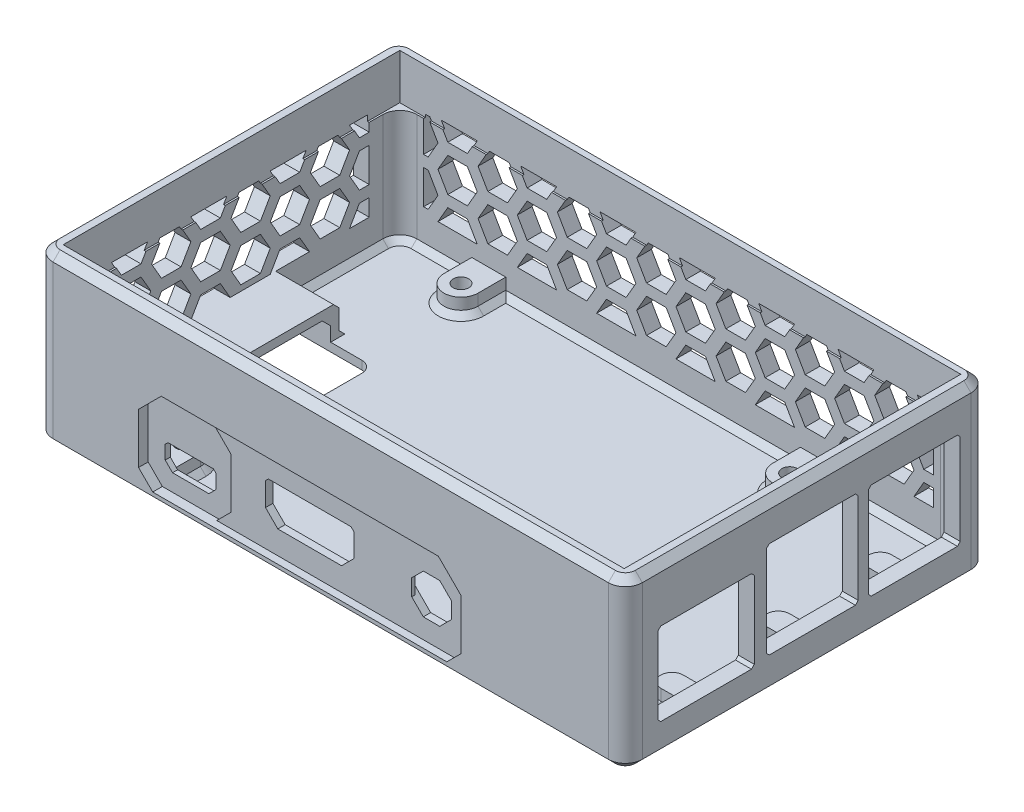
SolidWorks part; units mm, degrees
ref_plane "Front Plane" through (0, 0, 0) normal (0, 0, 1) x (1, 0, 0)
ref_plane "Top Plane" through (0, 0, 0) normal (0, 1, 0) x (1, 0, 0)
ref_plane "Right Plane" through (0, 0, 0) normal (1, 0, 0) x (0, 0, -1)
sketch "Sketch1" plane through (0, 0, 0) normal (0, 1, 0) x (1, 0, 0)
  line L0 (1, 28) -> (0, 28) construction
  line L1 (0, 0) -> (-85, 0) construction
  line L2 (0, 0) -> (0, 56) construction
  line L3 (0, 56) -> (-85, 56) construction
  line L4 (-85, 0) -> (-85, 56) construction
  line L5 (-97, 57.2) -> (1, 57.2) construction
  line L6 (-97, 57.2) -> (-97, -1.2) construction
  line L7 (-97, -1.2) -> (1, -1.2) construction
  line L8 (1, 57.2) -> (1, -1.2) construction
  circle A0 centre (-81.5, 52.5) radius 1.375 construction
  circle A1 centre (-23.5, 52.5) radius 1.375 construction
  circle A2 centre (-81.5, 3.5) radius 1.375 construction
  circle A3 centre (-23.5, 3.5) radius 1.375 construction
  dimension "D3" = 2.75
  dimension "D1" = 56
  dimension "D2" = 85
  dimension "D4" = 49
  dimension "D5" = 58
  dimension "D6" = 3.5
  dimension "D7" = 3.5
  dimension "D8" = 98
  dimension "D9" = 58.4
  dimension "D10" = 15.5
sketch "Sketch2" plane through (0, 0, 0) normal (0, 1, 0) x (1, 0, 0)
  line L0 (-84.5, -2.5) -> (-84.5, 3.5)
  line L2 (-78.5, 3.5) -> (-78.5, -2.5)
  line L3 (-81.5, 3.5) -> (-23.5, 3.5) construction
  line L4 (-81.5, 3.5) -> (-81.5, 52.5) construction
  line L5 (-52.5, 3.5) -> (-52.5, 28) construction
  line L6 (-52.5, 28) -> (-81.5, 28) construction
  line L7 (-84.5, -2.5) -> (-78.5, -2.5)
  line L8 (-20.5, -2.5) -> (-26.5, -2.5)
  line L9 (-26.5, 3.5) -> (-26.5, -2.5)
  line L10 (-20.5, -2.5) -> (-20.5, 3.5)
  line L11 (-20.5, 58.5) -> (-20.5, 52.5)
  line L12 (-26.5, 52.5) -> (-26.5, 58.5)
  line L13 (-20.5, 58.5) -> (-26.5, 58.5)
  line L14 (-84.5, 58.5) -> (-78.5, 58.5)
  line L15 (-78.5, 52.5) -> (-78.5, 58.5)
  line L16 (-84.5, 58.5) -> (-84.5, 52.5)
  arc A0 (-84.5, 3.5) -> (-78.5, 3.5) centre (-81.5, 3.5) cw
  circle A1 centre (-81.5, 3.5) radius 1.375 construction
  circle A2 centre (-81.5, 3.5) radius 1.375
  circle A3 centre (-23.5, 3.5) radius 1.375
  arc A4 (-20.5, 3.5) -> (-26.5, 3.5) centre (-23.5, 3.5) ccw
  arc A5 (-20.5, 52.5) -> (-26.5, 52.5) centre (-23.5, 52.5) cw
  circle A6 centre (-23.5, 52.5) radius 1.375
  circle A7 centre (-81.5, 52.5) radius 1.375
  arc A8 (-84.5, 52.5) -> (-78.5, 52.5) centre (-81.5, 52.5) ccw
  dimension "D1" = 2.75
  dimension "D2" = 6
  dimension "D3" = 6
extrude "Boss-Extrude1" add sketch "Sketch2" along normal blind 4.5
sketch "Sketch4" plane through (0, 0, 0) normal (0, 1, 0) x (1, 0, 0)
  line L0 (0, 28) -> (4, 28) construction
  line L1 (-100, 60) -> (4, 60)
  line L2 (-100, 60) -> (-100, -4)
  line L3 (-100, -4) -> (4, -4)
  line L4 (4, 60) -> (4, -4)
  line L5 (0, 0) -> (0, 56) construction
  line L7 (1, 57.2) -> (1, -1.2) construction
  line L9 (-97, 57.2) -> (-97, -1.2) construction
  dimension "D1" = 64
  dimension "D2" = 3
  dimension "D3" = 3
extrude "Boss-Extrude2" add sketch "Sketch4" along normal blind 1.5
sketch "Sketch5" plane through (0, 0, 0) normal (0, -1, 0) x (1, 0, 0)
  circle A0 centre (-81.5, -3.5) radius 2.6
  circle A1 centre (-23.5, -3.5) radius 2.6
  circle A2 centre (-23.5, -52.5) radius 2.6
  circle A3 centre (-81.5, -52.5) radius 2.6
  dimension "D1" = 5.2
extrude "Cut-Extrude1" cut sketch "Sketch5" against normal offset from surface (2.5 mm away) 2 up to face at (-81.5, 4.5, -1.25)
sketch "Sketch6" plane through (0, 1.5, 0) normal (0, 1, 0) x (1, 0, 0)
  line L0 (-97, 57.2) -> (-97, -1.2) construction
  line L1 (-100, 60) -> (4, 60)
  line L2 (-100, 60) -> (-100, -4)
  line L3 (-100, -4) -> (4, -4)
  line L4 (4, 60) -> (4, -4)
  line L5 (-97.5, 57.7) -> (1.5, 57.7)
  line L6 (-97.5, 57.7) -> (-97.5, -1.7)
  line L7 (-97.5, -1.7) -> (1.5, -1.7)
  line L8 (1.5, 57.7) -> (1.5, -1.7)
  line L9 (-97, 57.2) -> (1, 57.2) construction
  line L10 (1, 57.2) -> (1, -1.2) construction
  line L11 (-97, -1.2) -> (1, -1.2) construction
  dimension "D1" = 0.5
  dimension "D2" = 0.5
  dimension "D3" = 0.5
  dimension "D4" = 0.5
extrude "Boss-Extrude3" add sketch "Sketch6" along normal blind 28
sketch "Sketch10" plane through (0, 1.5, 0) normal (0, 1, 0) x (1, 0, 0)
  line L0 (1.5, 49) -> (-2, 49)
  line L1 (1.5, -1.7) -> (1.5, 57.7) construction
  line L2 (-2, 45) -> (1.5, 45)
  line L3 (1.5, 45) -> (1.5, 49)
  line L4 (1.5, 31) -> (-2, 31)
  line L5 (-2, 27) -> (1.5, 27)
  line L6 (1.5, 27) -> (1.5, 31)
  line L7 (1.5, 12.25) -> (-2, 12.25)
  line L8 (-2, 8.25) -> (1.5, 8.25)
  line L9 (1.5, 8.25) -> (1.5, 12.25)
  line L10 (0, 0) -> (0, 56) construction
  arc A0 (-2, 49) -> (-2, 45) centre (-2, 47) ccw
  arc A1 (-2, 31) -> (-2, 27) centre (-2, 29) ccw
  arc A2 (-2, 12.25) -> (-2, 8.25) centre (-2, 10.25) ccw
  point P19 (-4, 47)
  dimension "D1" = 4
  dimension "D2" = 4
  dimension "D3" = 10.25
  dimension "D4" = 29
  dimension "D5" = 47
extrude "Boss-Extrude4" add sketch "Sketch10" along normal up to surface (3 mm away) up to face at (-23.5, 4.5, -54.35)
sketch "Sketch18" plane through (0, 1.5, 0) normal (0, 1, 0) x (1, 0, 0)
  line L0 (-97.2, 57.4) -> (1.2, 57.4)
  line L1 (-97.5, 57.7) -> (1.5, 57.7)
  line L2 (-97.5, 57.7) -> (-97.5, -1.7)
  line L3 (-97.5, -1.7) -> (1.5, -1.7)
  line L4 (1.5, 57.7) -> (1.5, -1.7)
  line L5 (1.2, 57.4) -> (1.2, -1.4)
  line L6 (-97.2, -1.4) -> (1.2, -1.4)
  line L7 (-97.2, 57.4) -> (-97.2, -1.4)
  dimension "D1" = 0.3
extrude "Boss-Extrude6" add sketch "Sketch18" along normal blind 20
sketch "Sketch19" plane through (0, 0, -60) normal (0, 0, -1) x (-1, 0, 0)
  line L4 (5.5981, 8.5) -> (7.3301, 9.5) construction
  line L5 (6.4641, 7) -> (4.7321, 10)
  line L6 (4.7321, 10) -> (1.2679, 10)
  line L7 (1.2679, 10) -> (-0.4641, 7)
  line L8 (3, 7) -> (93, 7)
  line L9 (93, 7) -> (93, 22.5)
  line L10 (93, 22.5) -> (3, 22.5)
  line L11 (3, 22.5) -> (3, 7)
  line L12 (3, 7) -> (93, 7)
  line L13 (93, 7) -> (93, 22.5)
  line L14 (93, 22.5) -> (3, 22.5)
  line L15 (3, 22.5) -> (3, 7)
  line L16 (-0.4641, 7) -> (1.2679, 4)
  line L17 (1.2679, 4) -> (4.7321, 4)
  line L18 (4.7321, 4) -> (6.4641, 7)
  line L19 (11.6603, 14) -> (8.1962, 14)
  line L20 (8.1962, 14) -> (6.4641, 11)
  line L21 (6.4641, 11) -> (8.1962, 8)
  line L22 (8.1962, 8) -> (11.6603, 8)
  line L23 (11.6603, 8) -> (13.3923, 11)
  line L24 (13.3923, 11) -> (11.6603, 14)
  line L25 (20.4641, 7) -> (18.7321, 10)
  line L26 (18.7321, 10) -> (15.2679, 10)
  line L27 (15.2679, 10) -> (13.5359, 7)
  line L28 (13.5359, 7) -> (15.2679, 4)
  line L29 (15.2679, 4) -> (18.7321, 4)
  line L30 (18.7321, 4) -> (20.4641, 7)
  line L31 (25.6603, 14) -> (22.1962, 14)
  line L32 (22.1962, 14) -> (20.4641, 11)
  line L33 (20.4641, 11) -> (22.1962, 8)
  line L34 (22.1962, 8) -> (25.6603, 8)
  line L35 (25.6603, 8) -> (27.3923, 11)
  line L36 (27.3923, 11) -> (25.6603, 14)
  line L37 (19.5981, 8.5) -> (21.3301, 9.5) construction
  line L38 (34.4641, 7) -> (32.7321, 10)
  line L39 (32.7321, 10) -> (29.2679, 10)
  line L40 (29.2679, 10) -> (27.5359, 7)
  line L41 (27.5359, 7) -> (29.2679, 4)
  line L42 (29.2679, 4) -> (32.7321, 4)
  line L43 (32.7321, 4) -> (34.4641, 7)
  line L44 (39.6603, 14) -> (36.1962, 14)
  line L45 (36.1962, 14) -> (34.4641, 11)
  line L46 (34.4641, 11) -> (36.1962, 8)
  line L47 (36.1962, 8) -> (39.6603, 8)
  line L48 (39.6603, 8) -> (41.3923, 11)
  line L49 (41.3923, 11) -> (39.6603, 14)
  line L50 (33.5981, 8.5) -> (35.3301, 9.5) construction
  line L51 (48.4641, 7) -> (46.7321, 10)
  line L52 (46.7321, 10) -> (43.2679, 10)
  line L53 (43.2679, 10) -> (41.5359, 7)
  line L54 (41.5359, 7) -> (43.2679, 4)
  line L55 (43.2679, 4) -> (46.7321, 4)
  line L56 (46.7321, 4) -> (48.4641, 7)
  line L57 (53.6603, 14) -> (50.1962, 14)
  line L58 (50.1962, 14) -> (48.4641, 11)
  line L59 (48.4641, 11) -> (50.1962, 8)
  line L60 (50.1962, 8) -> (53.6603, 8)
  line L61 (53.6603, 8) -> (55.3923, 11)
  line L62 (55.3923, 11) -> (53.6603, 14)
  line L63 (47.5981, 8.5) -> (49.3301, 9.5) construction
  line L64 (62.4641, 7) -> (60.7321, 10)
  line L65 (60.7321, 10) -> (57.2679, 10)
  line L66 (57.2679, 10) -> (55.5359, 7)
  line L67 (55.5359, 7) -> (57.2679, 4)
  line L68 (57.2679, 4) -> (60.7321, 4)
  line L69 (60.7321, 4) -> (62.4641, 7)
  line L70 (67.6603, 14) -> (64.1962, 14)
  line L71 (64.1962, 14) -> (62.4641, 11)
  line L72 (62.4641, 11) -> (64.1962, 8)
  line L73 (64.1962, 8) -> (67.6603, 8)
  line L74 (67.6603, 8) -> (69.3923, 11)
  line L75 (69.3923, 11) -> (67.6603, 14)
  line L76 (61.5981, 8.5) -> (63.3301, 9.5) construction
  line L77 (76.4641, 7) -> (74.7321, 10)
  line L78 (74.7321, 10) -> (71.2679, 10)
  line L79 (71.2679, 10) -> (69.5359, 7)
  line L80 (69.5359, 7) -> (71.2679, 4)
  line L81 (71.2679, 4) -> (74.7321, 4)
  line L82 (74.7321, 4) -> (76.4641, 7)
  line L83 (81.6603, 14) -> (78.1962, 14)
  line L84 (78.1962, 14) -> (76.4641, 11)
  line L85 (76.4641, 11) -> (78.1962, 8)
  line L86 (78.1962, 8) -> (81.6603, 8)
  line L87 (81.6603, 8) -> (83.3923, 11)
  line L88 (83.3923, 11) -> (81.6603, 14)
  line L89 (75.5981, 8.5) -> (77.3301, 9.5) construction
  line L90 (90.4641, 7) -> (88.7321, 10)
  line L91 (88.7321, 10) -> (85.2679, 10)
  line L92 (85.2679, 10) -> (83.5359, 7)
  line L93 (83.5359, 7) -> (85.2679, 4)
  line L94 (85.2679, 4) -> (88.7321, 4)
  line L95 (88.7321, 4) -> (90.4641, 7)
  line L96 (95.6603, 14) -> (92.1962, 14)
  line L97 (92.1962, 14) -> (90.4641, 11)
  line L98 (90.4641, 11) -> (92.1962, 8)
  line L99 (92.1962, 8) -> (95.6603, 8)
  line L100 (95.6603, 8) -> (97.3923, 11)
  line L101 (97.3923, 11) -> (95.6603, 14)
  line L102 (89.5981, 8.5) -> (91.3301, 9.5) construction
  line L103 (20.4641, 15) -> (18.7321, 18)
  line L104 (18.7321, 18) -> (15.2679, 18)
  line L105 (15.2679, 18) -> (13.5359, 15)
  line L106 (13.5359, 15) -> (15.2679, 12)
  line L107 (15.2679, 12) -> (18.7321, 12)
  line L108 (18.7321, 12) -> (20.4641, 15)
  line L109 (25.6603, 22) -> (22.1962, 22)
  line L110 (22.1962, 22) -> (20.4641, 19)
  line L111 (20.4641, 19) -> (22.1962, 16)
  line L112 (22.1962, 16) -> (25.6603, 16)
  line L113 (25.6603, 16) -> (27.3923, 19)
  line L114 (27.3923, 19) -> (25.6603, 22)
  line L115 (19.5981, 16.5) -> (21.3301, 17.5) construction
  line L116 (34.4641, 15) -> (32.7321, 18)
  line L117 (32.7321, 18) -> (29.2679, 18)
  line L118 (29.2679, 18) -> (27.5359, 15)
  line L119 (27.5359, 15) -> (29.2679, 12)
  line L120 (29.2679, 12) -> (32.7321, 12)
  line L121 (32.7321, 12) -> (34.4641, 15)
  line L122 (39.6603, 22) -> (36.1962, 22)
  line L123 (36.1962, 22) -> (34.4641, 19)
  line L124 (34.4641, 19) -> (36.1962, 16)
  line L125 (36.1962, 16) -> (39.6603, 16)
  line L126 (39.6603, 16) -> (41.3923, 19)
  line L127 (41.3923, 19) -> (39.6603, 22)
  line L128 (33.5981, 16.5) -> (35.3301, 17.5) construction
  line L129 (48.4641, 15) -> (46.7321, 18)
  line L130 (46.7321, 18) -> (43.2679, 18)
  line L131 (43.2679, 18) -> (41.5359, 15)
  line L132 (41.5359, 15) -> (43.2679, 12)
  line L133 (43.2679, 12) -> (46.7321, 12)
  line L134 (46.7321, 12) -> (48.4641, 15)
  line L135 (53.6603, 22) -> (50.1962, 22)
  line L136 (50.1962, 22) -> (48.4641, 19)
  line L137 (48.4641, 19) -> (50.1962, 16)
  line L138 (50.1962, 16) -> (53.6603, 16)
  line L139 (53.6603, 16) -> (55.3923, 19)
  line L140 (55.3923, 19) -> (53.6603, 22)
  line L141 (47.5981, 16.5) -> (49.3301, 17.5) construction
  line L142 (62.4641, 15) -> (60.7321, 18)
  line L143 (60.7321, 18) -> (57.2679, 18)
  line L144 (57.2679, 18) -> (55.5359, 15)
  line L145 (55.5359, 15) -> (57.2679, 12)
  line L146 (57.2679, 12) -> (60.7321, 12)
  line L147 (60.7321, 12) -> (62.4641, 15)
  line L148 (67.6603, 22) -> (64.1962, 22)
  line L149 (64.1962, 22) -> (62.4641, 19)
  line L150 (62.4641, 19) -> (64.1962, 16)
  line L151 (64.1962, 16) -> (67.6603, 16)
  line L152 (67.6603, 16) -> (69.3923, 19)
  line L153 (69.3923, 19) -> (67.6603, 22)
  line L154 (61.5981, 16.5) -> (63.3301, 17.5) construction
  line L155 (76.4641, 15) -> (74.7321, 18)
  line L156 (74.7321, 18) -> (71.2679, 18)
  line L157 (71.2679, 18) -> (69.5359, 15)
  line L158 (69.5359, 15) -> (71.2679, 12)
  line L159 (71.2679, 12) -> (74.7321, 12)
  line L160 (74.7321, 12) -> (76.4641, 15)
  line L161 (81.6603, 22) -> (78.1962, 22)
  line L162 (78.1962, 22) -> (76.4641, 19)
  line L163 (76.4641, 19) -> (78.1962, 16)
  line L164 (78.1962, 16) -> (81.6603, 16)
  line L165 (81.6603, 16) -> (83.3923, 19)
  line L166 (83.3923, 19) -> (81.6603, 22)
  line L167 (75.5981, 16.5) -> (77.3301, 17.5) construction
  line L168 (90.4641, 15) -> (88.7321, 18)
  line L169 (88.7321, 18) -> (85.2679, 18)
  line L170 (85.2679, 18) -> (83.5359, 15)
  line L171 (83.5359, 15) -> (85.2679, 12)
  line L172 (85.2679, 12) -> (88.7321, 12)
  line L173 (88.7321, 12) -> (90.4641, 15)
  line L174 (95.6603, 22) -> (92.1962, 22)
  line L175 (92.1962, 22) -> (90.4641, 19)
  line L176 (90.4641, 19) -> (92.1962, 16)
  line L177 (92.1962, 16) -> (95.6603, 16)
  line L178 (95.6603, 16) -> (97.3923, 19)
  line L179 (97.3923, 19) -> (95.6603, 22)
  line L180 (89.5981, 16.5) -> (91.3301, 17.5) construction
  line L181 (20.4641, 23) -> (18.7321, 26)
  line L182 (18.7321, 26) -> (15.2679, 26)
  line L183 (15.2679, 26) -> (13.5359, 23)
  line L184 (13.5359, 23) -> (15.2679, 20)
  line L185 (15.2679, 20) -> (18.7321, 20)
  line L186 (18.7321, 20) -> (20.4641, 23)
  line L187 (25.6603, 30) -> (22.1962, 30)
  line L188 (22.1962, 30) -> (20.4641, 27)
  line L189 (20.4641, 27) -> (22.1962, 24)
  line L190 (22.1962, 24) -> (25.6603, 24)
  line L191 (25.6603, 24) -> (27.3923, 27)
  line L192 (27.3923, 27) -> (25.6603, 30)
  line L193 (19.5981, 24.5) -> (21.3301, 25.5) construction
  line L194 (34.4641, 23) -> (32.7321, 26)
  line L195 (32.7321, 26) -> (29.2679, 26)
  line L196 (29.2679, 26) -> (27.5359, 23)
  line L197 (27.5359, 23) -> (29.2679, 20)
  line L198 (29.2679, 20) -> (32.7321, 20)
  line L199 (32.7321, 20) -> (34.4641, 23)
  line L200 (39.6603, 30) -> (36.1962, 30)
  line L201 (36.1962, 30) -> (34.4641, 27)
  line L202 (34.4641, 27) -> (36.1962, 24)
  line L203 (36.1962, 24) -> (39.6603, 24)
  line L204 (39.6603, 24) -> (41.3923, 27)
  line L205 (41.3923, 27) -> (39.6603, 30)
  line L206 (33.5981, 24.5) -> (35.3301, 25.5) construction
  line L207 (48.4641, 23) -> (46.7321, 26)
  line L208 (46.7321, 26) -> (43.2679, 26)
  line L209 (43.2679, 26) -> (41.5359, 23)
  line L210 (41.5359, 23) -> (43.2679, 20)
  line L211 (43.2679, 20) -> (46.7321, 20)
  line L212 (46.7321, 20) -> (48.4641, 23)
  line L213 (53.6603, 30) -> (50.1962, 30)
  line L214 (50.1962, 30) -> (48.4641, 27)
  line L215 (48.4641, 27) -> (50.1962, 24)
  line L216 (50.1962, 24) -> (53.6603, 24)
  line L217 (53.6603, 24) -> (55.3923, 27)
  line L218 (55.3923, 27) -> (53.6603, 30)
  line L219 (47.5981, 24.5) -> (49.3301, 25.5) construction
  line L220 (62.4641, 23) -> (60.7321, 26)
  line L221 (60.7321, 26) -> (57.2679, 26)
  line L222 (57.2679, 26) -> (55.5359, 23)
  line L223 (55.5359, 23) -> (57.2679, 20)
  line L224 (57.2679, 20) -> (60.7321, 20)
  line L225 (60.7321, 20) -> (62.4641, 23)
  line L226 (67.6603, 30) -> (64.1962, 30)
  line L227 (64.1962, 30) -> (62.4641, 27)
  line L228 (62.4641, 27) -> (64.1962, 24)
  line L229 (64.1962, 24) -> (67.6603, 24)
  line L230 (67.6603, 24) -> (69.3923, 27)
  line L231 (69.3923, 27) -> (67.6603, 30)
  line L232 (61.5981, 24.5) -> (63.3301, 25.5) construction
  line L233 (76.4641, 23) -> (74.7321, 26)
  line L234 (74.7321, 26) -> (71.2679, 26)
  line L235 (71.2679, 26) -> (69.5359, 23)
  line L236 (69.5359, 23) -> (71.2679, 20)
  line L237 (71.2679, 20) -> (74.7321, 20)
  line L238 (74.7321, 20) -> (76.4641, 23)
  line L239 (81.6603, 30) -> (78.1962, 30)
  line L240 (78.1962, 30) -> (76.4641, 27)
  line L241 (76.4641, 27) -> (78.1962, 24)
  line L242 (78.1962, 24) -> (81.6603, 24)
  line L243 (81.6603, 24) -> (83.3923, 27)
  line L244 (83.3923, 27) -> (81.6603, 30)
  line L245 (75.5981, 24.5) -> (77.3301, 25.5) construction
  line L246 (90.4641, 23) -> (88.7321, 26)
  line L247 (88.7321, 26) -> (85.2679, 26)
  line L248 (85.2679, 26) -> (83.5359, 23)
  line L249 (83.5359, 23) -> (85.2679, 20)
  line L250 (85.2679, 20) -> (88.7321, 20)
  line L251 (88.7321, 20) -> (90.4641, 23)
  line L252 (95.6603, 30) -> (92.1962, 30)
  line L253 (92.1962, 30) -> (90.4641, 27)
  line L254 (90.4641, 27) -> (92.1962, 24)
  line L255 (92.1962, 24) -> (95.6603, 24)
  line L256 (95.6603, 24) -> (97.3923, 27)
  line L257 (97.3923, 27) -> (95.6603, 30)
  line L258 (89.5981, 24.5) -> (91.3301, 25.5) construction
  line L259 (6.4641, 15) -> (4.7321, 18)
  line L260 (4.7321, 18) -> (1.2679, 18)
  line L261 (1.2679, 18) -> (-0.4641, 15)
  line L262 (-0.4641, 15) -> (1.2679, 12)
  line L263 (1.2679, 12) -> (4.7321, 12)
  line L264 (4.7321, 12) -> (6.4641, 15)
  line L265 (11.6603, 22) -> (8.1962, 22)
  line L266 (8.1962, 22) -> (6.4641, 19)
  line L267 (6.4641, 19) -> (8.1962, 16)
  line L268 (8.1962, 16) -> (11.6603, 16)
  line L269 (11.6603, 16) -> (13.3923, 19)
  line L270 (13.3923, 19) -> (11.6603, 22)
  line L271 (5.5981, 16.5) -> (7.3301, 17.5) construction
  line L272 (6.4641, 23) -> (4.7321, 26)
  line L273 (4.7321, 26) -> (1.2679, 26)
  line L274 (1.2679, 26) -> (-0.4641, 23)
  line L275 (-0.4641, 23) -> (1.2679, 20)
  line L276 (1.2679, 20) -> (4.7321, 20)
  line L277 (4.7321, 20) -> (6.4641, 23)
  line L278 (11.6603, 30) -> (8.1962, 30)
  line L279 (8.1962, 30) -> (6.4641, 27)
  line L280 (6.4641, 27) -> (8.1962, 24)
  line L281 (8.1962, 24) -> (11.6603, 24)
  line L282 (11.6603, 24) -> (13.3923, 27)
  line L283 (13.3923, 27) -> (11.6603, 30)
  line L284 (5.5981, 24.5) -> (7.3301, 25.5) construction
  circle A0 centre (3, 7) radius 3 construction
  circle A1 centre (9.9282, 11) radius 3 construction
  circle A2 centre (17, 7) radius 3 construction
  circle A3 centre (23.9282, 11) radius 3 construction
  circle A4 centre (31, 7) radius 3 construction
  circle A5 centre (37.9282, 11) radius 3 construction
  circle A6 centre (45, 7) radius 3 construction
  circle A7 centre (51.9282, 11) radius 3 construction
  circle A8 centre (59, 7) radius 3 construction
  circle A9 centre (65.9282, 11) radius 3 construction
  circle A10 centre (73, 7) radius 3 construction
  circle A11 centre (79.9282, 11) radius 3 construction
  circle A12 centre (87, 7) radius 3 construction
  circle A13 centre (93.9282, 11) radius 3 construction
  circle A14 centre (17, 15) radius 3 construction
  circle A15 centre (23.9282, 19) radius 3 construction
  circle A16 centre (31, 15) radius 3 construction
  circle A17 centre (37.9282, 19) radius 3 construction
  circle A18 centre (45, 15) radius 3 construction
  circle A19 centre (51.9282, 19) radius 3 construction
  circle A20 centre (59, 15) radius 3 construction
  circle A21 centre (65.9282, 19) radius 3 construction
  circle A22 centre (73, 15) radius 3 construction
  circle A23 centre (79.9282, 19) radius 3 construction
  circle A24 centre (87, 15) radius 3 construction
  circle A25 centre (93.9282, 19) radius 3 construction
  circle A26 centre (17, 23) radius 3 construction
  circle A27 centre (23.9282, 27) radius 3 construction
  circle A28 centre (31, 23) radius 3 construction
  circle A29 centre (37.9282, 27) radius 3 construction
  circle A30 centre (45, 23) radius 3 construction
  circle A31 centre (51.9282, 27) radius 3 construction
  circle A32 centre (59, 23) radius 3 construction
  circle A33 centre (65.9282, 27) radius 3 construction
  circle A34 centre (73, 23) radius 3 construction
  circle A35 centre (79.9282, 27) radius 3 construction
  circle A36 centre (87, 23) radius 3 construction
  circle A37 centre (93.9282, 27) radius 3 construction
  circle A38 centre (3, 15) radius 3 construction
  circle A39 centre (9.9282, 19) radius 3 construction
  circle A40 centre (3, 23) radius 3 construction
  circle A41 centre (9.9282, 27) radius 3 construction
  dimension "D2" = 6
  dimension "D3" = 2
  dimension "D1" = 7
  dimension "D4" = 7
  dimension "D5" = 3
extrude "Cut-Extrude8" cut sketch "Sketch19" against normal up to next (2.6 mm away) contours L6 L15 L12 L5 | L263 L264 L259 L260 L15 | L276 L277 L14 L15 | L185 L186 L14 L184 | L269 L270 L265 L266 L267 L268 | L23 L24 L19 L20 L21 L22 | L107 L108 L103 L104 L105 L106 | L26 L27 L12 L25 | L35 L36 L31 L32 L33 L34 | L39 L40 L12 L38 | L48 L49 L44 L45 L46 L47 | L52 L53 L12 L51 | L61 L62 L57 L58 L59 L60 | L65 L66 L12 L64 | L74 L75 L70 L71 L72 L73 | L78 L79 L12 L77 | L87 L88 L83 L84 L85 L86 | L91 L92 L12 L90 | L98 L99 L13 L96 L97 | L176 L177 L13 L174 L175 | L250 L251 L14 L249 | L172 L173 L168 L169 L170 L171 | L165 L166 L161 L162 L163 L164 | L237 L238 L14 L236 | L159 L160 L155 L156 L157 L158 | L152 L153 L148 L149 L150 L151 | L224 L225 L14 L223 | L146 L147 L142 L143 L144 L145 | L139 L140 L135 L136 L137 L138 | L211 L212 L14 L210 | L198 L199 L14 L197 | L113 L114 L109 L110 L111 L112 | L120 L121 L116 L117 L118 L119 | L126 L127 L122 L123 L124 L125 | L133 L134 L129 L130 L131 L132 region at (-4.3472, 8.3333, -60) region at (-17, 8.3333, -60) region at (-4.3472, 15, -60) region at (-31, 8.3333, -60) region at (-4.2622, 21.3725, -60) region at (-45, 8.3333, -60) region at (-59, 8.3333, -60) region at (-17, 21.3725, -60) region at (-73, 8.3333, -60) region at (-31, 21.3725, -60) region at (-87, 8.3333, -60) region at (-45, 21.3725, -60) region at (-59, 21.3725, -60) region at (-92.0902, 11, -60) region at (-73, 21.3725, -60) region at (-92.0902, 19, -60) region at (-87, 21.3725, -60) region at (-9.9282, 11, -60) region at (-23.9282, 11, -60) region at (-37.9282, 11, -60) region at (-51.9282, 11, -60) region at (-65.9282, 11, -60) region at (-79.9282, 11, -60) region at (-17, 15, -60) region at (-23.9282, 19, -60) region at (-31, 15, -60) region at (-37.9282, 19, -60) region at (-45, 15, -60) region at (-51.9282, 19, -60) region at (-59, 15, -60) region at (-65.9282, 19, -60) region at (-73, 15, -60) region at (-79.9282, 19, -60) region at (-87, 15, -60) region at (-9.9282, 19, -60)
sketch "Sketch21" plane through (-100, 0, 0) normal (-1, 0, 0) x (0, 0, 1)
  line L0 (-60, 29.5) -> (4, 29.5) construction
  line L1 (-52, 22.5) -> (-4, 22.5)
  line L2 (-52, 22.5) -> (-52, 7)
  line L3 (-52, 7) -> (-4, 7)
  line L4 (-4, 22.5) -> (-4, 7)
  line L5 (-60, 0) -> (4, 0) construction
  line L6 (-60, 29.5) -> (-60, 0) construction
  line L7 (4, 29.5) -> (4, 0) construction
  line L8 (-52, 7) -> (-45.0718, 11) construction
  line L9 (-53.7321, 10) -> (-55.4641, 7)
  line L10 (-55.4641, 7) -> (-53.7321, 4)
  line L11 (-53.7321, 4) -> (-50.2679, 4)
  line L12 (-50.2679, 4) -> (-48.5359, 7)
  line L13 (-48.5359, 7) -> (-50.2679, 10)
  line L14 (-50.2679, 10) -> (-53.7321, 10)
  line L15 (-43.3397, 14) -> (-46.8038, 14)
  line L16 (-46.8038, 14) -> (-48.5359, 11)
  line L17 (-48.5359, 11) -> (-46.8038, 8)
  line L18 (-46.8038, 8) -> (-43.3397, 8)
  line L19 (-43.3397, 8) -> (-41.6077, 11)
  line L20 (-41.6077, 11) -> (-43.3397, 14)
  line L21 (-39.7321, 10) -> (-41.4641, 7)
  line L22 (-41.4641, 7) -> (-39.7321, 4)
  line L23 (-39.7321, 4) -> (-36.2679, 4)
  line L24 (-36.2679, 4) -> (-34.5359, 7)
  line L25 (-34.5359, 7) -> (-36.2679, 10)
  line L26 (-36.2679, 10) -> (-39.7321, 10)
  line L27 (-29.3397, 14) -> (-32.8038, 14)
  line L28 (-32.8038, 14) -> (-34.5359, 11)
  line L29 (-34.5359, 11) -> (-32.8038, 8)
  line L30 (-32.8038, 8) -> (-29.3397, 8)
  line L31 (-29.3397, 8) -> (-27.6077, 11)
  line L32 (-27.6077, 11) -> (-29.3397, 14)
  line L33 (-38, 7) -> (-31.0718, 11) construction
  line L34 (-25.7321, 10) -> (-27.4641, 7)
  line L35 (-27.4641, 7) -> (-25.7321, 4)
  line L36 (-25.7321, 4) -> (-22.2679, 4)
  line L37 (-22.2679, 4) -> (-20.5359, 7)
  line L38 (-20.5359, 7) -> (-22.2679, 10)
  line L39 (-22.2679, 10) -> (-25.7321, 10)
  line L40 (-15.3397, 14) -> (-18.8038, 14)
  line L41 (-18.8038, 14) -> (-20.5359, 11)
  line L42 (-20.5359, 11) -> (-18.8038, 8)
  line L43 (-18.8038, 8) -> (-15.3397, 8)
  line L44 (-15.3397, 8) -> (-13.6077, 11)
  line L45 (-13.6077, 11) -> (-15.3397, 14)
  line L46 (-24, 7) -> (-17.0718, 11) construction
  line L47 (-11.7321, 10) -> (-13.4641, 7)
  line L48 (-13.4641, 7) -> (-11.7321, 4)
  line L49 (-11.7321, 4) -> (-8.2679, 4)
  line L50 (-8.2679, 4) -> (-6.5359, 7)
  line L51 (-6.5359, 7) -> (-8.2679, 10)
  line L52 (-8.2679, 10) -> (-11.7321, 10)
  line L53 (-1.3397, 14) -> (-4.8038, 14)
  line L54 (-4.8038, 14) -> (-6.5359, 11)
  line L55 (-6.5359, 11) -> (-4.8038, 8)
  line L56 (-4.8038, 8) -> (-1.3397, 8)
  line L57 (-1.3397, 8) -> (0.3923, 11)
  line L58 (0.3923, 11) -> (-1.3397, 14)
  line L59 (-10, 7) -> (-3.0718, 11) construction
  line L60 (-39.7321, 18) -> (-41.4641, 15)
  line L61 (-41.4641, 15) -> (-39.7321, 12)
  line L62 (-39.7321, 12) -> (-36.2679, 12)
  line L63 (-36.2679, 12) -> (-34.5359, 15)
  line L64 (-34.5359, 15) -> (-36.2679, 18)
  line L65 (-36.2679, 18) -> (-39.7321, 18)
  line L66 (-29.3397, 22) -> (-32.8038, 22)
  line L67 (-32.8038, 22) -> (-34.5359, 19)
  line L68 (-34.5359, 19) -> (-32.8038, 16)
  line L69 (-32.8038, 16) -> (-29.3397, 16)
  line L70 (-29.3397, 16) -> (-27.6077, 19)
  line L71 (-27.6077, 19) -> (-29.3397, 22)
  line L72 (-38, 15) -> (-31.0718, 19) construction
  line L73 (-25.7321, 18) -> (-27.4641, 15)
  line L74 (-27.4641, 15) -> (-25.7321, 12)
  line L75 (-25.7321, 12) -> (-22.2679, 12)
  line L76 (-22.2679, 12) -> (-20.5359, 15)
  line L77 (-20.5359, 15) -> (-22.2679, 18)
  line L78 (-22.2679, 18) -> (-25.7321, 18)
  line L79 (-15.3397, 22) -> (-18.8038, 22)
  line L80 (-18.8038, 22) -> (-20.5359, 19)
  line L81 (-20.5359, 19) -> (-18.8038, 16)
  line L82 (-18.8038, 16) -> (-15.3397, 16)
  line L83 (-15.3397, 16) -> (-13.6077, 19)
  line L84 (-13.6077, 19) -> (-15.3397, 22)
  line L85 (-24, 15) -> (-17.0718, 19) construction
  line L86 (-11.7321, 18) -> (-13.4641, 15)
  line L87 (-13.4641, 15) -> (-11.7321, 12)
  line L88 (-11.7321, 12) -> (-8.2679, 12)
  line L89 (-8.2679, 12) -> (-6.5359, 15)
  line L90 (-6.5359, 15) -> (-8.2679, 18)
  line L91 (-8.2679, 18) -> (-11.7321, 18)
  line L92 (-1.3397, 22) -> (-4.8038, 22)
  line L93 (-4.8038, 22) -> (-6.5359, 19)
  line L94 (-6.5359, 19) -> (-4.8038, 16)
  line L95 (-4.8038, 16) -> (-1.3397, 16)
  line L96 (-1.3397, 16) -> (0.3923, 19)
  line L97 (0.3923, 19) -> (-1.3397, 22)
  line L98 (-10, 15) -> (-3.0718, 19) construction
  line L99 (-39.7321, 26) -> (-41.4641, 23)
  line L100 (-41.4641, 23) -> (-39.7321, 20)
  line L101 (-39.7321, 20) -> (-36.2679, 20)
  line L102 (-36.2679, 20) -> (-34.5359, 23)
  line L103 (-34.5359, 23) -> (-36.2679, 26)
  line L104 (-36.2679, 26) -> (-39.7321, 26)
  line L105 (-29.3397, 30) -> (-32.8038, 30)
  line L106 (-32.8038, 30) -> (-34.5359, 27)
  line L107 (-34.5359, 27) -> (-32.8038, 24)
  line L108 (-32.8038, 24) -> (-29.3397, 24)
  line L109 (-29.3397, 24) -> (-27.6077, 27)
  line L110 (-27.6077, 27) -> (-29.3397, 30)
  line L111 (-38, 23) -> (-31.0718, 27) construction
  line L112 (-25.7321, 26) -> (-27.4641, 23)
  line L113 (-27.4641, 23) -> (-25.7321, 20)
  line L114 (-25.7321, 20) -> (-22.2679, 20)
  line L115 (-22.2679, 20) -> (-20.5359, 23)
  line L116 (-20.5359, 23) -> (-22.2679, 26)
  line L117 (-22.2679, 26) -> (-25.7321, 26)
  line L118 (-15.3397, 30) -> (-18.8038, 30)
  line L119 (-18.8038, 30) -> (-20.5359, 27)
  line L120 (-20.5359, 27) -> (-18.8038, 24)
  line L121 (-18.8038, 24) -> (-15.3397, 24)
  line L122 (-15.3397, 24) -> (-13.6077, 27)
  line L123 (-13.6077, 27) -> (-15.3397, 30)
  line L124 (-24, 23) -> (-17.0718, 27) construction
  line L125 (-11.7321, 26) -> (-13.4641, 23)
  line L126 (-13.4641, 23) -> (-11.7321, 20)
  line L127 (-11.7321, 20) -> (-8.2679, 20)
  line L128 (-8.2679, 20) -> (-6.5359, 23)
  line L129 (-6.5359, 23) -> (-8.2679, 26)
  line L130 (-8.2679, 26) -> (-11.7321, 26)
  line L131 (-1.3397, 30) -> (-4.8038, 30)
  line L132 (-4.8038, 30) -> (-6.5359, 27)
  line L133 (-6.5359, 27) -> (-4.8038, 24)
  line L134 (-4.8038, 24) -> (-1.3397, 24)
  line L135 (-1.3397, 24) -> (0.3923, 27)
  line L136 (0.3923, 27) -> (-1.3397, 30)
  line L137 (-10, 23) -> (-3.0718, 27) construction
  line L138 (-53.7321, 18) -> (-55.4641, 15)
  line L139 (-55.4641, 15) -> (-53.7321, 12)
  line L140 (-53.7321, 12) -> (-50.2679, 12)
  line L141 (-50.2679, 12) -> (-48.5359, 15)
  line L142 (-48.5359, 15) -> (-50.2679, 18)
  line L143 (-50.2679, 18) -> (-53.7321, 18)
  line L144 (-43.3397, 22) -> (-46.8038, 22)
  line L145 (-46.8038, 22) -> (-48.5359, 19)
  line L146 (-48.5359, 19) -> (-46.8038, 16)
  line L147 (-46.8038, 16) -> (-43.3397, 16)
  line L148 (-43.3397, 16) -> (-41.6077, 19)
  line L149 (-41.6077, 19) -> (-43.3397, 22)
  line L150 (-52, 15) -> (-45.0718, 19) construction
  line L151 (-53.7321, 26) -> (-55.4641, 23)
  line L152 (-55.4641, 23) -> (-53.7321, 20)
  line L153 (-53.7321, 20) -> (-50.2679, 20)
  line L154 (-50.2679, 20) -> (-48.5359, 23)
  line L155 (-48.5359, 23) -> (-50.2679, 26)
  line L156 (-50.2679, 26) -> (-53.7321, 26)
  line L157 (-43.3397, 30) -> (-46.8038, 30)
  line L158 (-46.8038, 30) -> (-48.5359, 27)
  line L159 (-48.5359, 27) -> (-46.8038, 24)
  line L160 (-46.8038, 24) -> (-43.3397, 24)
  line L161 (-43.3397, 24) -> (-41.6077, 27)
  line L162 (-41.6077, 27) -> (-43.3397, 30)
  line L163 (-52, 23) -> (-45.0718, 27) construction
  circle A0 centre (-52, 7) radius 3 construction
  circle A1 centre (-45.0718, 11) radius 3 construction
  circle A2 centre (-38, 7) radius 3 construction
  circle A3 centre (-31.0718, 11) radius 3 construction
  circle A4 centre (-24, 7) radius 3 construction
  circle A5 centre (-17.0718, 11) radius 3 construction
  circle A6 centre (-10, 7) radius 3 construction
  circle A7 centre (-3.0718, 11) radius 3 construction
  circle A8 centre (-38, 15) radius 3 construction
  circle A9 centre (-31.0718, 19) radius 3 construction
  circle A10 centre (-24, 15) radius 3 construction
  circle A11 centre (-17.0718, 19) radius 3 construction
  circle A12 centre (-10, 15) radius 3 construction
  circle A13 centre (-3.0718, 19) radius 3 construction
  circle A14 centre (-38, 23) radius 3 construction
  circle A15 centre (-31.0718, 27) radius 3 construction
  circle A16 centre (-24, 23) radius 3 construction
  circle A17 centre (-17.0718, 27) radius 3 construction
  circle A18 centre (-10, 23) radius 3 construction
  circle A19 centre (-3.0718, 27) radius 3 construction
  circle A20 centre (-52, 15) radius 3 construction
  circle A21 centre (-45.0718, 19) radius 3 construction
  circle A22 centre (-52, 23) radius 3 construction
  circle A23 centre (-45.0718, 27) radius 3 construction
  point P8 (-52, 14.75)
  dimension "D1" = 7
  dimension "D2" = 7
  dimension "D3" = 8
  dimension "D4" = 8
  dimension "D5" = 2
  dimension "D6" = 6
  dimension "D7" = 4
  dimension "D8" = 3
extrude "Cut-Extrude9" cut sketch "Sketch21" against normal blind 10 contours L13 L14 L2 L3 | L142 L143 L2 L140 L141 | L153 L154 L1 L2 | L148 L149 L144 L145 L146 L147 | L101 L102 L1 L100 | L70 L71 L66 L67 L68 L69 | L114 L115 L1 L113 | L127 L128 L1 L126 | L94 L95 L4 L92 L93 | L55 L56 L4 L53 L54 | L51 L52 L47 L3 | L38 L39 L34 L3 | L25 L26 L21 L3 | L19 L20 L15 L16 L17 L18 | L64 L65 L60 L61 L62 L63 | L31 L32 L27 L28 L29 L30 | L77 L78 L73 L74 L75 L76 | L44 L45 L40 L41 L42 L43 | L90 L91 L86 L87 L88 L89 | L83 L84 L79 L80 L81 L82 region at (-100, 21.3725, -50.7378) region at (-100, 21.3725, -38) region at (-100, 15, -50.6528) region at (-100, 21.3725, -24) region at (-100, 8.3333, -50.6528) region at (-100, 21.3725, -10) region at (-100, 8.3333, -38) region at (-100, 19, -4.9098) region at (-100, 8.3333, -24) region at (-100, 11, -4.9098) region at (-100, 8.3333, -10) region at (-100, 11, -45.0718) region at (-100, 11, -31.0718) region at (-100, 11, -17.0718) region at (-100, 15, -38) region at (-100, 19, -31.0718) region at (-100, 15, -24) region at (-100, 19, -17.0718) region at (-100, 15, -10) region at (-100, 19, -45.0718)
sketch "Sketch8" plane through (0, 0, 0) normal (0, 0, 1) x (1, 0, 0)
  line L0 (-85, 5.9) -> (-85, 4.5) construction
  line L1 (0, 5.9) -> (-85, 5.9) construction
  line L3 (-60.5, 12.5) -> (-45.5, 12.5) construction
  line L4 (-45.5, 12.5) -> (-45.5, 8.3) construction
  line L5 (-45.5, 8.3) -> (-47.5, 6.3) construction
  line L6 (-47.5, 6.3) -> (-58.5, 6.3) construction
  line L7 (-58.5, 6.3) -> (-60.5, 8.3) construction
  line L8 (-60.5, 8.3) -> (-60.5, 12.5) construction
  line L9 (-78.4, 8.6) -> (-70.4, 8.6) construction
  line L10 (-70.4, 8.6) -> (-70.4, 6.4) construction
  line L11 (-70.4, 6.4) -> (-71.4, 5.4) construction
  line L12 (-71.4, 5.4) -> (-77.4, 5.4) construction
  line L13 (-77.4, 5.4) -> (-78.4, 6.4) construction
  line L14 (-78.4, 6.4) -> (-78.4, 8.6) construction
  line L15 (-85, 4.5) -> (0, 4.5) construction
  line L16 (0, 4.5) -> (0, 5.9) construction
  line L17 (-60.8, 12.8) -> (-45.2, 12.8)
  line L18 (-45.2, 12.8) -> (-45.2, 8.1757)
  line L19 (-45.2, 8.1757) -> (-47.3757, 6)
  line L20 (-47.3757, 6) -> (-58.6243, 6)
  line L21 (-58.6243, 6) -> (-60.8, 8.1757)
  line L22 (-60.8, 8.1757) -> (-60.8, 12.8)
  line L23 (-78.9, 9.1) -> (-69.9, 9.1)
  line L24 (-69.9, 9.1) -> (-69.9, 6.1929)
  line L25 (-69.9, 6.1929) -> (-71.1929, 4.9)
  line L26 (-71.1929, 4.9) -> (-77.6071, 4.9)
  line L27 (-77.6071, 4.9) -> (-78.9, 6.1929)
  line L28 (-78.9, 6.1929) -> (-78.9, 9.1)
  line L29 (-22.125, 4.5) -> (-24.875, 4.5) construction
  line L30 (-28, 10.3497) -> (-30.0503, 12.4)
  line L31 (-32.9497, 12.4) -> (-35, 10.3497)
  line L32 (-35, 10.3497) -> (-35, 7.4503)
  line L33 (-35, 7.4503) -> (-32.9497, 5.4)
  line L34 (-32.9497, 5.4) -> (-30.0503, 5.4)
  line L35 (-30.0503, 5.4) -> (-28, 7.4503)
  line L36 (-28, 7.4503) -> (-28, 10.3497)
  line L37 (-30.0503, 12.4) -> (-32.9497, 12.4)
  circle A0 centre (-31.5, 8.9) radius 3 construction
  circle A1 centre (-31.5, 8.9) radius 3.5 construction
  point P9 (-53, 6.3)
  point P21 (-74.4, 5.4)
  dimension "D1" = 6
  dimension "D16" = 0.5
  dimension "D2" = 1.4
  dimension "D3" = 53.5
  dimension "D4" = 45
  dimension "D5" = 6.2
  dimension "D6" = 15
  dimension "D7" = 6.6
  dimension "D8" = 11
  dimension "D9" = 32
  dimension "D10" = 45
  dimension "D11" = 8
  dimension "D12" = 3.2
  dimension "D13" = 0.5
  dimension "D14" = 1
  dimension "D15" = 10.6
  dimension "D17" = 0.3
  dimension "D18" = 0.5
extrude "Cut-Extrude2" cut sketch "Sketch8" along normal through all
sketch "Sketch9" plane through (0, 0, 0) normal (1, 0, 0) x (0, 0, -1)
  line L0 (0, 4.5) -> (56.2337, 4.5) construction
  line L1 (2.25, 19.5) -> (18.25, 19.5) construction
  line L2 (2.25, 19.5) -> (2.25, 5.9) construction
  line L3 (2.25, 5.9) -> (18.25, 5.9) construction
  line L4 (18.25, 19.5) -> (18.25, 5.9) construction
  line L5 (21.4, 22.5) -> (36.6, 22.5) construction
  line L6 (21.4, 22.5) -> (21.4, 6.5) construction
  line L7 (21.4, 6.5) -> (36.6, 6.5) construction
  line L8 (36.6, 22.5) -> (36.6, 6.5) construction
  line L9 (39.4, 22.5) -> (54.6, 22.5) construction
  line L10 (39.4, 22.5) -> (39.4, 6.5) construction
  line L11 (39.4, 6.5) -> (54.6, 6.5) construction
  line L12 (54.6, 22.5) -> (54.6, 6.5) construction
  line L13 (56.2337, 4.5) -> (56.2337, 5.9) construction
  line L14 (56.2337, 5.9) -> (0, 5.9) construction
  line L15 (0, 5.9) -> (0, 4.5) construction
  line L16 (1.75, 20) -> (1.75, 5.4)
  line L17 (1.75, 5.4) -> (18.75, 5.4)
  line L18 (18.75, 20) -> (18.75, 5.4)
  line L19 (1.75, 20) -> (18.75, 20)
  line L20 (20.9, 23) -> (20.9, 6)
  line L21 (20.9, 6) -> (37.1, 6)
  line L22 (37.1, 23) -> (37.1, 6)
  line L23 (20.9, 23) -> (37.1, 23)
  line L24 (38.9, 23) -> (38.9, 6)
  line L25 (38.9, 6) -> (55.1, 6)
  line L26 (55.1, 23) -> (55.1, 6)
  line L27 (38.9, 23) -> (55.1, 23)
  point P16 (10.25, 5.9)
  point P19 (29, 6.5)
  point P21 (47, 6.5)
  dimension "D1" = 13.6
  dimension "D2" = 16
  dimension "D3" = 15.2
  dimension "D4" = 16
  dimension "D5" = 2
  dimension "D6" = 10.25
  dimension "D7" = 29
  dimension "D8" = 47
  dimension "D9" = 0.5
extrude "Cut-Extrude3" cut sketch "Sketch9" along normal through all
sketch "Sketch11" plane through (0, 0, 4) normal (0, 0, 1) x (1, 0, 0)
  line L0 (-78.9, 9.1) -> (-78.9, 6.1929) construction
  line L1 (-81.9, 15.8) -> (-25, 15.8)
  line L2 (-81.9, 15.8) -> (-81.9, 1.9)
  line L3 (-81.9, 1.9) -> (-25, 1.9)
  line L4 (-25, 15.8) -> (-25, 1.9)
  line L5 (-45.2, 12.8) -> (-60.8, 12.8) construction
  line L6 (-77.6071, 4.9) -> (-71.1929, 4.9) construction
  line L7 (-28, 7.4503) -> (-28, 10.3497) construction
  dimension "D1" = 3
  dimension "D2" = 3
  dimension "D3" = 3
  dimension "D4" = 3
extrude "Cut-Extrude4" cut sketch "Sketch11" against normal blind 1.3
sketch "Sketch12" plane through (0, 0, 2.7) normal (0, 0, 1) x (1, 0, 0)
  line L0 (-81.9, 1.9) -> (-25, 1.9) construction
  line L1 (-81.9, 1.9) -> (-66.9, 1.9)
  line L2 (-81.9, 1.9) -> (-81.9, 15.8)
  line L3 (-81.9, 15.8) -> (-66.9, 15.8)
  line L4 (-66.9, 1.9) -> (-66.9, 15.8)
  line L5 (-81.9, 15.8) -> (-81.9, 1.9) construction
  line L6 (-25, 15.8) -> (-81.9, 15.8) construction
  line L7 (-69.9, 6.1929) -> (-69.9, 9.1) construction
  dimension "D1" = 3
extrude "Cut-Extrude5" cut sketch "Sketch12" against normal blind 0.4
fillet "Fillet1" radius 3 8 edges at (-100, 14.75, -60) (4, 14.75, -60) (-100, 14.75, 4) (4, 14.75, 4) (1.2, 11.5, 1.4) (1.2, 11.5, -57.4) (-97.2, 11.5, -57.4) (-97.2, 11.5, 1.4)
chamfer "Chamfer5" distance 2.5 angle 45 6 edges at (-25, 1.9, 3.35) (-81.9, 1.9, 3.15) (-66.9, 1.9, 2.5) (-66.9, 15.8, 2.5) (-81.9, 15.8, 3.15) (-25, 15.8, 3.35)
chamfer "Chamfer1" distance 0.5 angle 45 16 edges at (-45.2, 12.8, 2.05) (-60.8, 12.8, 2.05) (-69.9, 9.1, 1.85) (-78.9, 9.1, 1.85) (2.75, 23, -55.1) (2.6, 6, -38.9) (2.75, 23, -38.9) (2.5586, 6, -55.1) (2.6, 6, -37.1) (2.75, 23, -37.1) (2.75, 23, -20.9) (2.6, 6, -20.9) (2.6, 5.4, -18.75) (2.6, 20, -18.75) (2.6, 20, -1.75) (2.6, 5.4, -1.75)
sketch "Sketch20" plane through (0, 1.5, 0) normal (0, 1, 0) x (1, 0, 0)
  line L1 (-100, 36.5) -> (-87, 36.5)
  line L2 (-100, 36.5) -> (-100, 19.5)
  line L3 (-100, 19.5) -> (-87, 19.5)
  line L4 (-87, 36.5) -> (-87, 19.5)
  line L5 (-85, 28) -> (-100, 28) construction
  line L6 (-85, 0) -> (-85, 56) construction
  line L7 (-100, 57) -> (-100, -1) construction
  dimension "D1" = 2
  dimension "D2" = 17
extrude "Boss-Extrude7" add sketch "Sketch20" along normal blind 5.5
chamfer "Chamfer7" distance 1.25 angle 45 16 edges at (4, 0, -28) (-48, 0, 4) (-100, 0, -28) (-48, 0, -60) (4, 29.5, -28) (-48, 29.5, 4) (-100, 29.5, -28) (3.1213, 0, 3.1213) (-99.1213, 0, 3.1213) (3.1213, 0, -59.1213) (-99.1213, 0, -59.1213) (3.1213, 29.5, -59.1213) (3.1213, 29.5, 3.1213) (-99.1213, 29.5, -59.1213) (-99.1213, 29.5, 3.1213) (-48, 29.5, -60)
chamfer "Chamfer3" distance 1 angle 45 41 edges at (-26.5, 1.5, -1.05) (-20.5, 1.5, -1.05) (-23.5, 1.5, -6.5) (-78.5, 1.5, -1.05) (-84.5, 1.5, -1.05) (-81.5, 1.5, -6.5) (-20.5, 1.5, -54.95) (-26.5, 1.5, -54.95) (-23.5, 1.5, -49.5) (-78.5, 1.5, -54.95) (-84.5, 1.5, -54.95) (-81.5, 1.5, -49.5) (-0.4, 1.5, -12.25) (-0.4, 1.5, -8.25) (-4, 1.5, -10.25) (-0.4, 1.5, -31) (-0.4, 1.5, -27) (-4, 1.5, -29) (-0.4, 1.5, -49) (-0.4, 1.5, -45) (-4, 1.5, -47) (-89.35, 1.5, -57.4) (-89.35, 1.5, 1.4) (-52.5, 1.5, 1.4) (1.2, 1.5, -19.625) (1.2, 1.5, -4.925) (-11.15, 1.5, 1.4) (1.2, 1.5, -38) (-11.15, 1.5, -57.4) (1.2, 1.5, -51.7) (-52.5, 1.5, -57.4) (-96.3213, 1.5, -56.5213) (-96.3213, 1.5, 0.5213) (0.3213, 1.5, 0.5213) (0.3213, 1.5, -56.5213) (-97.2, 1.5, -10.55) (-97.2, 1.5, -45.45) (-92.1, 7, -36.5) (-92.1, 7, -19.5) (-92.1, 1.5, -19.5) (-92.1, 1.5, -36.5)
sketch "Sketch14" plane through (0, 1.5, 0) normal (0, 1, 0) x (1, 0, 0)
  line L0 (-81.5, 33) -> (-81.5, 23) construction
  line L1 (-79.5, 33) -> (-79.5, 23)
  line L2 (-79.5, 28) -> (-81.5, 28) construction
  line L3 (-81.5, 52.5) -> (-81.5, 3.5) construction
  line L4 (-81.5, 21) -> (-100, 21)
  line L5 (-100, 21) -> (-100, 35)
  line L6 (-100, 35) -> (-81.5, 35)
  line L7 (-100, -1) -> (-100, 57) construction
  arc A0 (-79.5, 33) -> (-81.5, 35) centre (-81.5, 33) ccw
  arc A1 (-81.5, 21) -> (-79.5, 23) centre (-81.5, 23) ccw
  point P2 (-81.5, 28)
  dimension "D1" = 2
  dimension "D2" = 10
extrude "Cut-Extrude6" cut sketch "Sketch14" against normal through all and the other way blind 4
chamfer "Chamfer9" distance 1.5 angle 45 3 edges at (-53.45, 15.8, 4) (-93.5, 5.5, -21) (-93.5, 5.5, -35)
chamfer "Chamfer10" distance 0.7 angle 45 4 edges at (-35, 8.9, 1.4) (-29.0251, 11.3749, 1.4) (-31.5, 12.4, 1.4) (-33.9749, 11.3749, 1.4)
